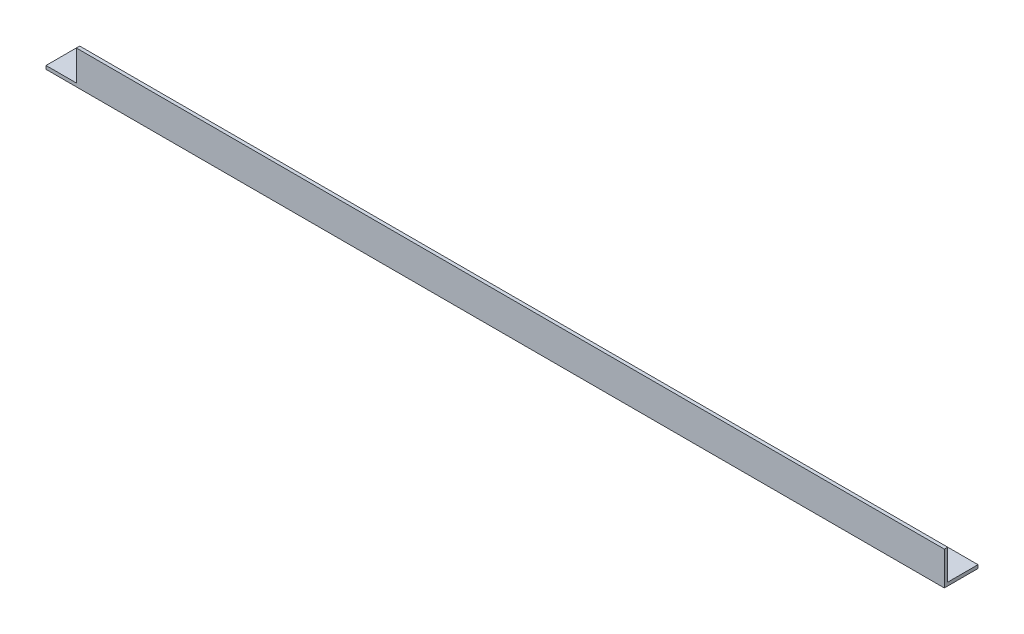
SolidWorks part; units mm, degrees
ref_plane "Спереди" through (0, 0, 0) normal (0, 0, 1) x (1, 0, 0)
ref_plane "Сверху" through (0, 0, 0) normal (0, 1, 0) x (1, 0, 0)
ref_plane "Справа" through (0, 0, 0) normal (1, 0, 0) x (0, 0, -1)
sketch "Эскиз1" plane through (0, 0, 0) normal (1, 0, 0) x (0, 0, -1)
  line L0 (0, 0) -> (30, 0)
  line L1 (0, 0) -> (0, 30)
extrude "Вытянуть-Тонкостенный1" add sketch "Эскиз1" along normal blind 800 thin thin type one direction wall 3
sketch "Эскиз2" plane through (0, 0, 0) normal (0, 0, 1) x (1, 0, 0)
  line L1 (0, 30) -> (27, 30)
  line L2 (0, 30) -> (0, 3)
  line L3 (0, 3) -> (27, 3)
  line L4 (27, 30) -> (27, 3)
extrude "Вырез-Вытянуть1" cut sketch "Эскиз2" against normal through all
